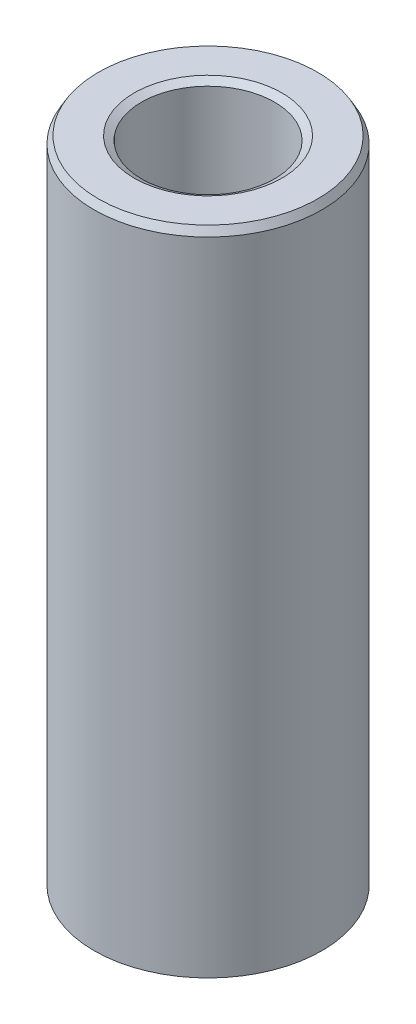
SolidWorks part; units mm, degrees
ref_plane "Front Plane" through (0, 0, 0) normal (0, 0, 1) x (1, 0, 0)
ref_plane "Top Plane" through (0, 0, 0) normal (0, 1, 0) x (1, 0, 0)
ref_plane "Right Plane" through (0, 0, 0) normal (1, 0, 0) x (0, 0, -1)
sketch "Sketch1" plane through (0, 0, 0) normal (0, 1, 0) x (1, 0, 0)
  circle A0 centre (0, 0) radius 30
  dimension "SLEEVE_OD" = 60
extrude "Boss-Extrude1" add sketch "Sketch1" along normal blind 172.0035
sketch "Sketch2" plane through (0, 0, 0) normal (0, 1, 0) x (1, 0, 0)
  circle A0 centre (0, 0) radius 17.5141
  dimension "BORE_D" = 35.0283
extrude "Cut-Extrude1" cut sketch "Sketch2" along normal through all
chamfer "Chamfer1" distance 1.9456 angle 30 4 edges at (0, 172.0035, 17.5141) (0, 0, 17.5141) (0, 0, 30) (0, 172.0035, 30) first distance on face at (0, 172.0035, 17.5141) first distance on face at (0, 0, 17.5141) first distance on face at (0, 172.0035, 30)
